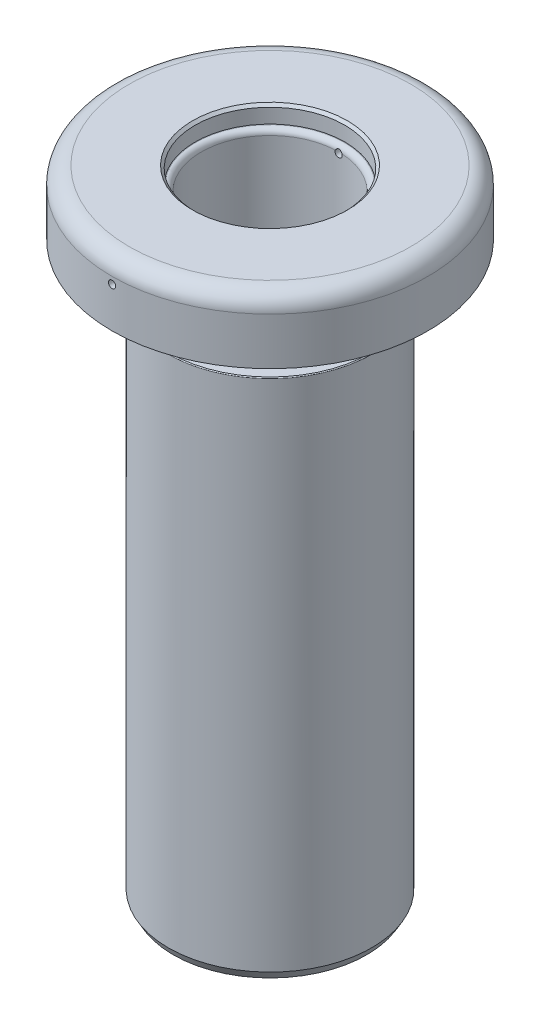
SolidWorks part; units mm, degrees
ref_plane "Front Plane" through (0, 0, 0) normal (0, 0, 1) x (1, 0, 0)
ref_plane "Top Plane" through (0, 0, 0) normal (0, 1, 0) x (1, 0, 0)
ref_plane "Right Plane" through (0, 0, 0) normal (1, 0, 0) x (0, 0, -1)
sketch "Sketch1" plane through (0, 0, 0) normal (0, 0, 1) x (1, 0, 0)
  line L0 (0, 0) -> (0, 19200.2562) construction
  line L1 (-11.0744, -0.381) -> (-11.0744, -2.54)
  line L2 (-11.0744, -2.54) -> (-10.16, -2.54)
  line L3 (-10.16, -2.54) -> (-10.16, -93.98)
  line L4 (-10.16, -93.98) -> (-15.0495, -93.98)
  line L5 (-15.0495, -16.5608) -> (-15.0495, -93.98)
  line L6 (-15.0495, -9.525) -> (-17.3736, -9.525)
  line L7 (-23.368, -9.525) -> (-23.368, 0)
  line L8 (-23.368, 0) -> (-11.4554, 0)
  line L9 (-11.4554, 0) -> (-11.0744, -0.381)
  line L10 (-15.0495, -12.954) -> (-13.0175, -12.954)
  line L11 (-13.0175, -12.954) -> (-13.0175, -16.5608)
  line L12 (-13.0175, -16.5608) -> (-15.0495, -16.5608)
  line L13 (-15.0495, -12.954) -> (-15.0495, -9.525)
  line L14 (-20.9042, -9.525) -> (-20.9042, -7.5692)
  line L15 (-20.9042, -7.5692) -> (-17.3736, -7.5692)
  line L16 (-17.3736, -7.5692) -> (-17.3736, -9.525)
  line L19 (-20.9042, -9.525) -> (-23.368, -9.525)
  dimension "D1" = 20.32
  dimension "D2" = 22.1488
  dimension "D3" = 45
  dimension "D4" = 0.381
  dimension "D5" = 2.54
  dimension "D6" = 30.099
  dimension "D7" = 46.736
  dimension "D8" = 9.525
  dimension "D9" = 93.98
  dimension "D10" = 3.6068
  dimension "D11" = 3.429
  dimension "D12" = 26.035
  dimension "D14" = 1.9558
  dimension "D15" = 34.7472
  dimension "D16" = 3.5306
revolve "Revolve1" add sketch "Sketch1" angle 360 about L0
sketch "Sketch2" plane through (0, 0, 0) normal (0, 0, 1) x (1, 0, 0)
  line L0 (11.0744, -2.54) -> (-11.0744, -2.54) construction
  circle A0 centre (0, -3.556) radius 0.5334
  dimension "D1" = 1.0668
  dimension "D2" = 1.016
extrude "Cut-Extrude1" cut sketch "Sketch2" against normal through all and the other way through all contours A0
fillet "Fillet2" radius 0.8128 1 edges at (0, -2.54, -10.16)
fillet "Fillet3" radius 2.54 1 edges at (0, 0, -23.368)
chamfer "Chamfer1" distance 1.27 angle 30 1 edges at (0, -93.98, -15.0495) first distance on face at (0, -93.98, -15.0495)
fillet "Fillet5" radius 0.254 2 edges at (0, -16.5608, -13.0175) (0, -12.954, -13.0175)
fillet "Fillet6" radius 0.127 4 edges at (0, -12.954, -15.0495) (0, -9.525, -17.3736) (0, -9.525, -20.9042) (0, -16.5608, -15.0495)
fillet "Fillet7" radius 0.254 2 edges at (0, -7.5692, -20.9042) (0, -7.5692, -17.3736)
